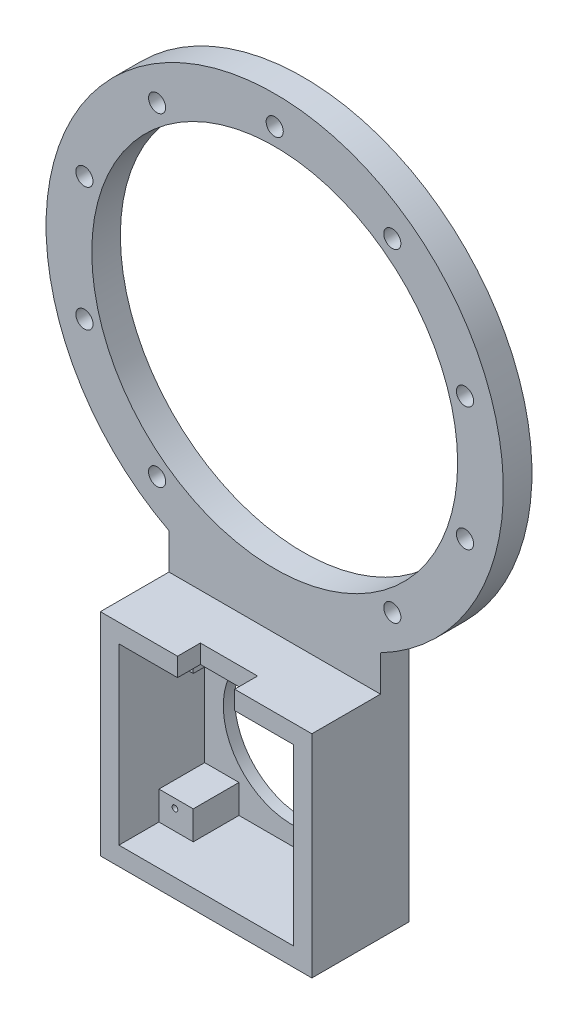
SolidWorks part; units mm, degrees
note: The reader was unsure of these and kept them because the rebuilt part matched: shared geometry of "Sketch1<31>", "Sketch1<32>", "Sketch1<33>".
ref_plane "Front Plane" through (0, 0, 0) normal (0, 0, 1) x (1, 0, 0)
ref_plane "Top Plane" through (0, 0, 0) normal (0, 1, 0) x (1, 0, 0)
ref_plane "Right Plane" through (0, 0, 0) normal (1, 0, 0) x (0, 0, -1)
sketch "Sketch1" plane through (0, 0, 0) normal (0, 0, 1) x (1, 0, 0)
  line L27 (0, 0) -> (0, -78.7335) construction
  line L28 (15.25, -60.2335) -> (-15.25, -60.2335) construction
  line L29 (18.5, -78.7335) -> (-18.5, -78.7335)
  line L31 (-18.5, -78.7335) -> (-18.5, -35.4648)
  line L32 (18.5, -78.7335) -> (18.5, -35.4648)
  line L33 (15.25, -44.9835) -> (-15.25, -44.9835)
  line L34 (15.25, -44.9835) -> (15.25, -75.4835)
  line L35 (15.25, -75.4835) -> (-15.25, -75.4835)
  line L36 (-15.25, -44.9835) -> (-15.25, -75.4835)
  line L37 (15.25, -44.9835) -> (-15.25, -75.4835) construction
  line L38 (15.25, -75.4835) -> (-15.25, -44.9835) construction
  line L40 (9.25, -44.9835) -> (9.25, -49.9835)
  line L41 (-15.25, -44.9835) -> (-9.25, -44.9835)
  line L42 (-15.25, -44.9835) -> (-15.25, -49.9835)
  line L43 (-15.25, -49.9835) -> (-9.25, -49.9835)
  line L44 (-9.25, -44.9835) -> (-9.25, -49.9835)
  line L45 (15.25, -49.9835) -> (9.25, -49.9835)
  line L46 (15.25, -44.9835) -> (15.25, -49.9835)
  line L47 (15.25, -44.9835) -> (9.25, -44.9835)
  line L48 (15.25, -75.4835) -> (9.25, -75.4835)
  line L49 (15.25, -75.4835) -> (15.25, -70.4835)
  line L50 (15.25, -70.4835) -> (9.25, -70.4835)
  line L51 (-9.25, -75.4835) -> (-9.25, -70.4835)
  line L52 (-15.25, -70.4835) -> (-9.25, -70.4835)
  line L53 (-15.25, -75.4835) -> (-15.25, -70.4835)
  line L54 (-15.25, -75.4835) -> (-9.25, -75.4835)
  line L55 (9.25, -75.4835) -> (9.25, -70.4835)
  line L56 (15.25, -75.4835) -> (-15.25, -75.4835)
  line L57 (-18.5, -41.7335) -> (18.5, -41.7335)
  circle A1 centre (0, 0) radius 32
  circle A4 centre (0, 35) radius 1.5
  circle A5 centre (20.5725, 28.3156) radius 1.5
  circle A6 centre (33.287, 10.8156) radius 1.5
  circle A7 centre (33.287, -10.8156) radius 1.5
  circle A8 centre (20.5725, -28.3156) radius 1.5
  circle A10 centre (-20.5725, -28.3156) radius 1.5
  circle A11 centre (-33.287, -10.8156) radius 1.5
  circle A12 centre (-33.287, 10.8156) radius 1.5
  circle A13 centre (-20.5725, 28.3156) radius 1.5
  circle A14 centre (0, -35) radius 1.5 [skipped]
  arc A16 (18.5, -35.4648) -> (-18.5, -35.4648) centre (0, 0) ccw
  circle A17 centre (0, -60.2335) radius 12
  circle A18 centre (12.45, -48.4565) radius 0.5
  circle A19 centre (-12.45, -48.4565) radius 0.5
  circle A20 centre (12.45, -72.0104) radius 0.5
  circle A21 centre (-12.45, -72.0104) radius 0.5
  point P6 (2.5, -43.3322)
  point P15 (0, -78.7335)
  point P34 (0, 0)
  point P48 (2.5, -77.1347)
  point P49 (2.5, -64.3322)
  point P51 (2.5, -64.3322)
  dimension "D2" = 64
  dimension "D5" = 3.25
  dimension "D6" = 24
  dimension "D7" = 5
  dimension "D8" = 10
  dimension "D10" = 6
  dimension "D9" = 40
  dimension "D3" = 30.5
  dimension "D4" = 30.5
  dimension "D12" = 1
  dimension "D13" = 2.8
  dimension "D11" = 3.25
  dimension "D14" = 3.25
  dimension "D15" = 37
extrude "Boss-Extrude1" add sketch "Sketch1" along normal blind 5
extrude "Boss-Extrude2" add sketch "Sketch1<31>" along normal blind 2 separate body contours L35 L55 L50 L34 L45 L40 L33 L44 L43 L36 L52 L51 A17
sketch "Sketch1<31>" plane through (0, 0, 0) normal (0, 0, 1) x (1, 0, 0) same geometry as "Sketch1"
extrude "Boss-Extrude3" add sketch "Sketch1<32>" along normal blind 10 contours L44 L33 L36 L43 A19 | L45 L34 L33 L40 A18 | L55 L35 L34 L50 A20 | L52 L36 L35 L51 A21
sketch "Sketch1<32>" plane through (0, 0, 0) normal (0, 0, 1) x (1, 0, 0) same geometry as "Sketch1"
extrude "Boss-Extrude4" add sketch "Sketch1<33>" along normal blind 17 contours L57 L31 L29 L32 L36 L33 L34 L35
sketch "Sketch1<33>" plane through (0, 0, 0) normal (0, 0, 1) x (1, 0, 0) same geometry as "Sketch1"
sketch "Sketch2" plane through (0, -44.9835, 0) normal (0, -1, 0) x (1, 0, 0)
  line L0 (5, 17) -> (-5, 17)
  line L1 (18.5, 17) -> (-18.5, 17) construction
  line L2 (-5, 17) -> (-5, 13)
  line L3 (-5, 13) -> (5, 13)
  line L4 (5, 13) -> (5, 17)
  point P5 (0, 17)
  dimension "D1" = 4
  dimension "10" = 10
extrude "Cut-Extrude1" cut sketch "Sketch2" against normal blind 3.25
sketch "Sketch3" plane through (0, 0, 5) normal (0, 0, 1) x (1, 0, 0)
  circle A1 centre (0, 35) radius 3
  circle A2 centre (20.5725, 28.3156) radius 3
  circle A3 centre (33.287, 10.8156) radius 3
  circle A4 centre (33.287, -10.8156) radius 3
  circle A5 centre (20.5725, -28.3156) radius 3
  circle A7 centre (-20.5725, -28.3156) radius 3
  circle A8 centre (-33.287, -10.8156) radius 3
  circle A9 centre (-33.287, 10.8156) radius 3
  circle A10 centre (-20.5725, 28.3156) radius 3
  circle A11 centre (0, -35) radius 3 [skipped]
  point P27 (0, 0)
  dimension "D1" = 10
